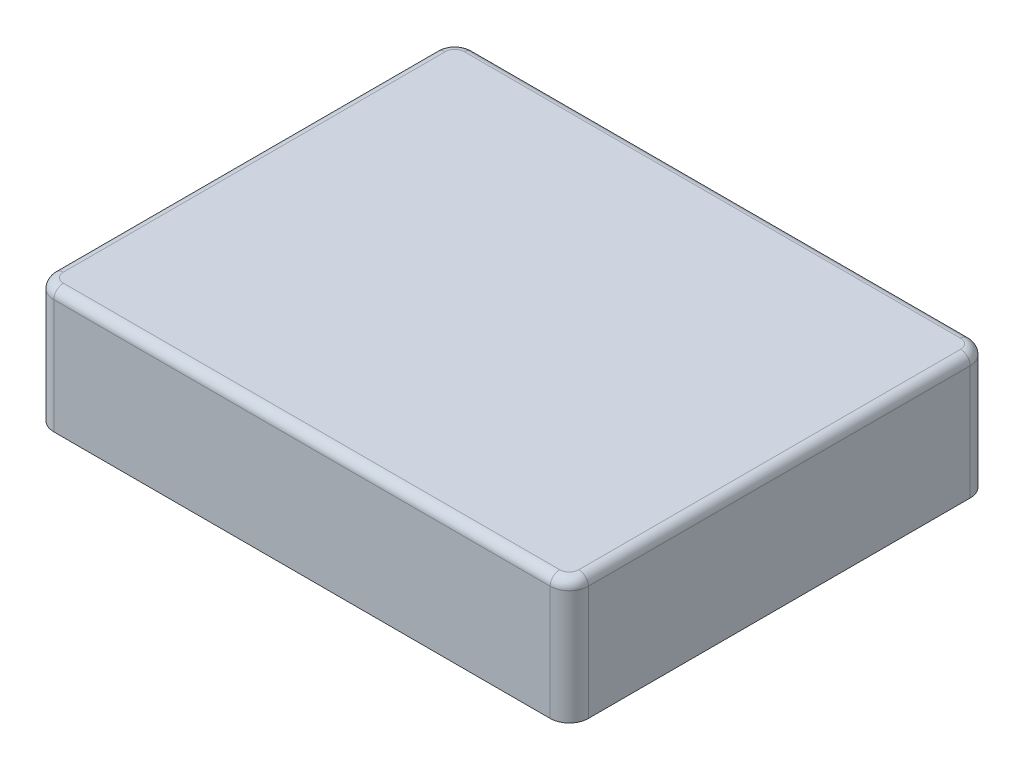
SolidWorks part; units mm, degrees
ref_plane "Front Plane" through (0, 0, 0) normal (0, 0, 1) x (1, 0, 0)
ref_plane "Top Plane" through (0, 0, 0) normal (0, 1, 0) x (1, 0, 0)
ref_plane "Right Plane" through (0, 0, 0) normal (1, 0, 0) x (0, 0, -1)
sketch "Sketch1" plane through (0, 0, 0) normal (0, 1, 0) x (1, 0, 0)
  line L1 (-28, 22) -> (28, 22)
  line L2 (-28, 22) -> (-28, -22)
  line L3 (-28, -22) -> (28, -22)
  line L4 (28, 22) -> (28, -22)
  dimension "D1" = 22
  dimension "D2" = 56
  dimension "D3" = 44
  dimension "D4" = 28
extrude "Boss-Extrude1" add sketch "Sketch1" along normal blind 13
fillet "Fillet1" radius 1 4 edges at (0, 13, -22) (28, 13, 0) (0, 13, 22) (-28, 13, 0)
fillet "Fillet2" radius 2 8 edges at (27.7071, 12.7071, -21.7071) (27.7071, 12.7071, 21.7071) (-27.7071, 12.7071, 21.7071) (-27.7071, 12.7071, -21.7071) (28, 6, -22) (28, 6, 22) (-28, 6, 22) (-28, 6, -22)
